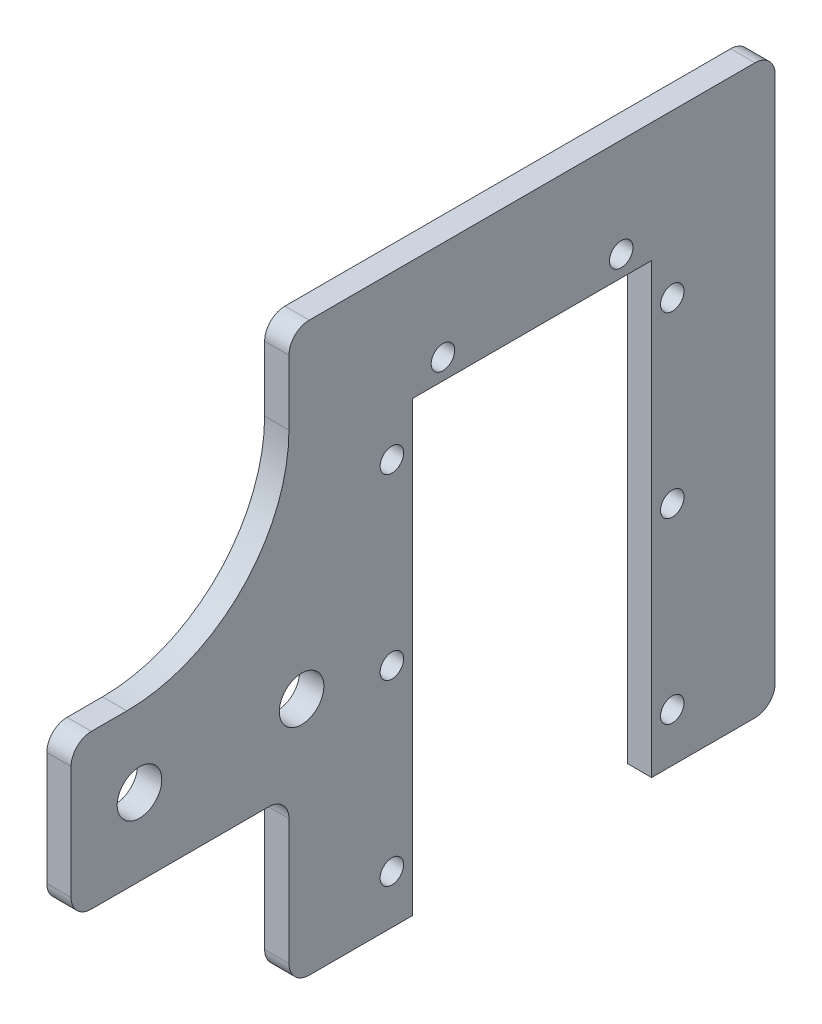
SolidWorks part; units mm, degrees
ref_plane "Front Plane" through (0, 0, 0) normal (0, 0, 1) x (1, 0, 0)
ref_plane "Top Plane" through (0, 0, 0) normal (0, 1, 0) x (1, 0, 0)
ref_plane "Right Plane" through (0, 0, 0) normal (1, 0, 0) x (0, 0, -1)
sketch "Mounting points" plane through (0, 0, 0) normal (1, 0, 0) x (0, 0, -1)
  line L0 (-17.3, 0) -> (17.3, 0) construction
  line L1 (-17.3, 18) -> (-17.3, 40) construction
  line L2 (17.3, 18) -> (17.3, 40) construction
  line L3 (-17.3, 18) -> (-17.3, -4) construction
  line L4 (17.3, 18) -> (17.3, -4) construction
  line L5 (11, 47.8) -> (-11, 47.8) construction
  line L6 (14.5, 45) -> (-14.5, 45) construction
  line L7 (14.5, 45) -> (14.5, -14.5) construction
  line L8 (14.5, -14.5) -> (-14.5, -14.5) construction
  line L9 (-14.5, 45) -> (-14.5, -14.5) construction
  line L10 (0, 50.8505) -> (0, -49949.1495) construction
  point P5 (0, 0)
  point P18 (0, 47.8)
  dimension "D1" = 34.6
  dimension "D2" = 22
  dimension "D3" = 4
  dimension "D4" = 29
  dimension "D5" = 14.5
  dimension "D6" = 45
  dimension "D7" = 22
  dimension "D8" = 47.8
sketch "Sketch11" plane through (0, 0, 0) normal (1, 0, 0) x (0, 0, -1)
  line L0 (-56.88, 16.5) -> (-56.88, 23.5) construction
  line L1 (-56.88, 10.5) -> (-56.88, 29.5)
  line L2 (-56.88, 10.5) -> (-20, 10.5)
  line L3 (-20, 10.5) -> (-20, 29.5)
  line L4 (-56.88, 29.5) -> (-20, 29.5)
  line L6 (-520, 29.5) -> (-20, 29.5) construction
  line L7 (-20, 23.5) -> (-20, 16.5) construction
  point P6 (-56.88, 20)
extrude "Boss-Extrude3" add sketch "Sketch11" along normal mid plane 3 separate body
sketch "Sketch8" plane through (0, 0, 0) normal (1, 0, 0) x (0, 0, -1)
  line L0 (30, 60) -> (-30, 60)
  line L9 (-17.3, 0) -> (17.3, 0) construction
  line L10 (30, 60) -> (30, -10)
  line L11 (14.75, -10) -> (30, -10)
  line L12 (-14.75, 45.25) -> (-14.75, -14.5)
  line L13 (14.75, 45.25) -> (-14.75, 45.25)
  line L14 (14.75, -14.5) -> (14.75, 45.25)
  line L15 (-14.75, 45.25) -> (-14.75, -10)
  line L16 (0, 200050.8505) -> (0, -249949.1495) construction
  line L17 (-30, 60) -> (-30, -10)
  line L18 (-30, -10) -> (-14.75, -10)
  line L24 (14.75, 45.25) -> (-14.75, 45.25)
  line L25 (14.75, -10) -> (14.75, 45.25)
  dimension "D2" = 60
  dimension "D3" = 10
  dimension "D4" = 30
  dimension "D5" = 30
  dimension "D1" = 0.25
extrude "Boss-Extrude2" add sketch "Sketch8" along normal mid plane 3
hole_wizard "M5 Clearance Hole1" positions "Sketch10" profile "Sketch9" hole size "M5" standard "ANSI Metric" end condition up to next
sketch "Sketch10" plane through (1.5, 0, 0) normal (1, 0, 0) x (0, 0, -1)
  circle A0 centre (-48.44, 20) radius 2.1 construction
  circle A1 centre (-28.44, 20) radius 2.1 construction
  point P0 (-48.44, 20)
  point P5 (-28.44, 20)
sketch "Sketch9" plane through (1.5, 20, 48.44) normal (0, 1, 0) x (0, 0, -1)
  line L0 (0, 0) -> (0, 3)
  line L1 (0, 3) -> (2.75, 3)
  line L2 (2.75, 3) -> (2.75, 0)
  line L5 (2.75, 0) -> (0, 0)
  line L11 (0, -6.35) -> (0, 107.95) construction
  dimension "Thru Hole Dia." = 5.5
  dimension "Thru Hole Depth" = 3
fillet "Fillet1" radius 2.5 2 edges at (0, 10.5, 56.88) (0, 29.5, 56.88)
fillet "Fillet2" radius 2.5 5 edges at (0, -10, -30) (0, -10, 30) (0, 60, -30) (0, 60, 30) (0, 10.5, 30)
hole_wizard "M2.5 Clearance Hole1" positions "Sketch14" profile "Sketch13" hole size "M2.5" standard "ANSI Metric" end condition up to next
sketch "Sketch14" plane through (1.5, 0, 0) normal (1, 0, 0) x (0, 0, -1)
  point P0 (17.3, 40)
  point P4 (79.7283, 74.7436)
  point P6 (17.3, 18)
  point P9 (17.3, -4)
  point P12 (-17.3, -4)
  point P15 (-17.3, 18)
  point P18 (-17.3, 40)
  point P21 (-11, 47.8)
  point P24 (11, 47.8)
sketch "Sketch13" plane through (1.5, 40, -17.3) normal (0, 1, 0) x (0, 0, -1)
  line L0 (0, 0) -> (0, 3)
  line L1 (0, 3) -> (1.45, 3)
  line L2 (1.45, 3) -> (1.45, 0)
  line L5 (1.45, 0) -> (0, 0)
  line L11 (0, -6.35) -> (0, 107.95) construction
  dimension "Thru Hole Dia." = 2.9
  dimension "Thru Hole Depth" = 3
fillet "Fillet3" radius 20 1 edges at (0, 29.5, 30)
